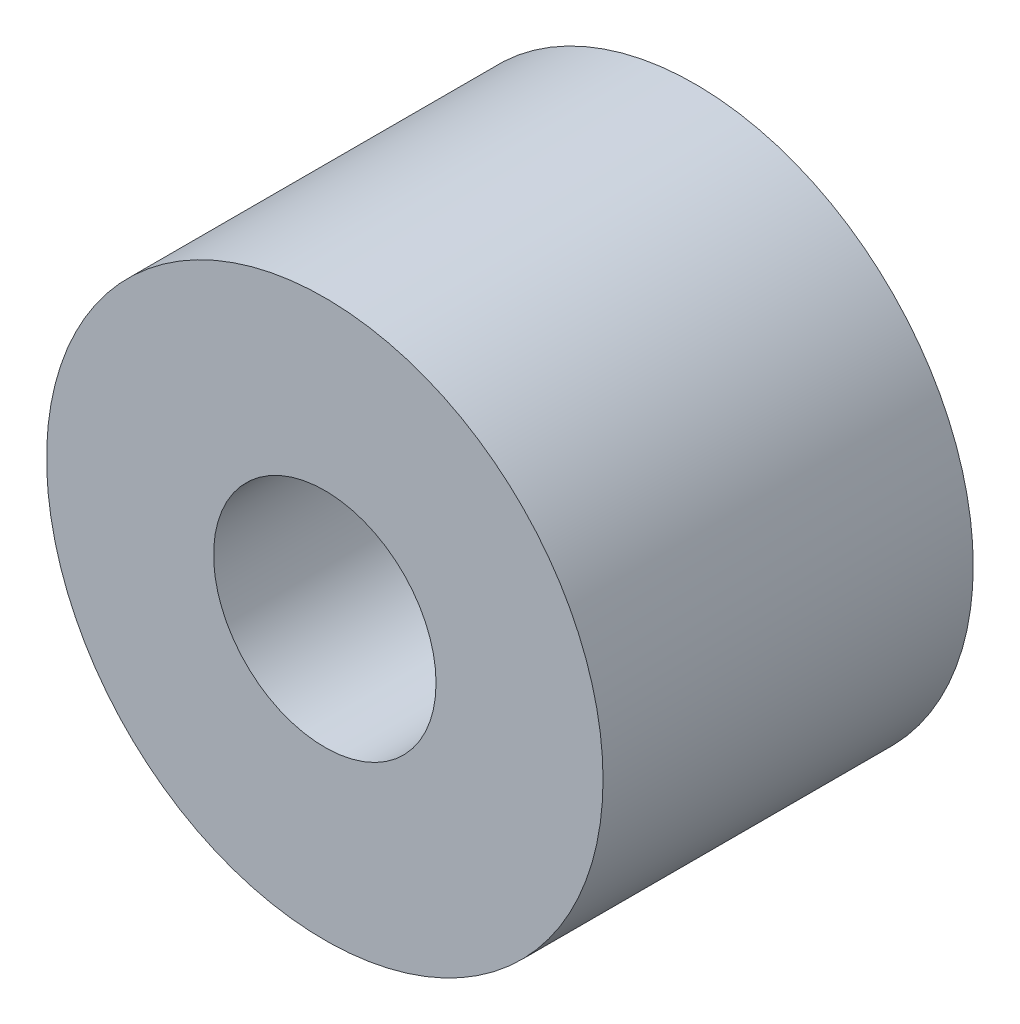
SolidWorks part; units mm, degrees
ref_plane "Płaszczyzna przednia" through (0, 0, 0) normal (0, 0, 1) x (1, 0, 0)
ref_plane "Płaszczyzna górna" through (0, 0, 0) normal (0, 1, 0) x (1, 0, 0)
ref_plane "Płaszczyzna prawa" through (0, 0, 0) normal (1, 0, 0) x (0, 0, -1)
sketch "Szkic2" plane through (0, 0, 0) normal (0, 0, 1) x (1, 0, 0)
  circle A0 centre (0, 0) radius 381
  circle A1 centre (0, 0) radius 953
  dimension "D1" = 762
  dimension "D2" = 1906
extrude "Dodanie-wyciągnięcie1" add sketch "Szkic2" along normal blind 1268 contours A0 | A1
ref_axis "Oś1" through (0, 0, 1268) along (0, 0, -1)
